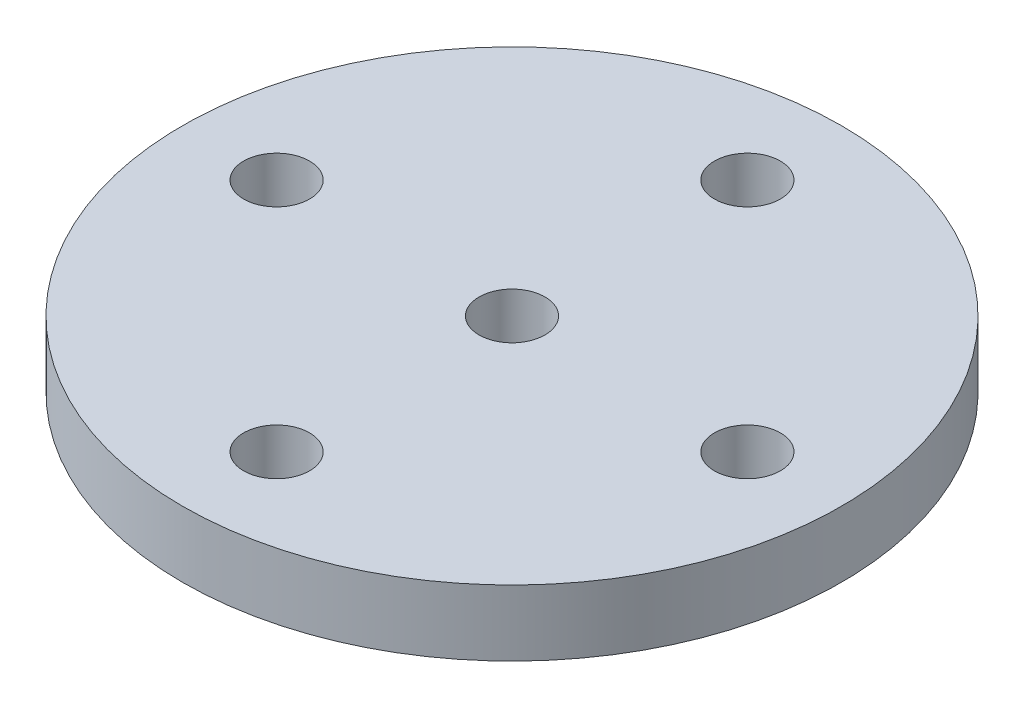
SolidWorks part; units mm, degrees
ref_plane "Front Plane" through (0, 0, 0) normal (0, 0, 1) x (1, 0, 0)
ref_plane "Top Plane" through (0, 0, 0) normal (0, 1, 0) x (1, 0, 0)
ref_plane "Right Plane" through (0, 0, 0) normal (1, 0, 0) x (0, 0, -1)
sketch "Sketch1" plane through (0, 0, 0) normal (0, 1, 0) x (1, 0, 0)
  circle A0 centre (0, 0) radius 17.5
  circle A1 centre (0, 0) radius 12.5
  circle A2 centre (0, 0) radius 1.75
  circle A3 centre (0, 12.5) radius 1.75
  circle A4 centre (-12.5, 0) radius 1.75
  circle A5 centre (0, -12.5) radius 1.75
  circle A6 centre (12.5, 0) radius 1.75
  dimension "D1" = 35
  dimension "D2" = 25
  dimension "D3" = 3.5
  dimension "D4" = 3.5
  dimension "D5" = 3.5
  dimension "D6" = 3.5
  dimension "D7" = 3.5
extrude "Boss-Extrude1" add sketch "Sketch1" along normal blind 3.5 contours A0
extrude "Cut-Extrude1" cut sketch "Sketch1<3>" along normal up to surface (3.5 mm away) contours A4 | A3 | A6 | A2 | A5 up to face at (0, 3.5, 17.5)
sketch "Sketch1<3>" plane through (0, 0, 0) normal (0, 1, 0) x (1, 0, 0) same geometry as "Sketch1"
